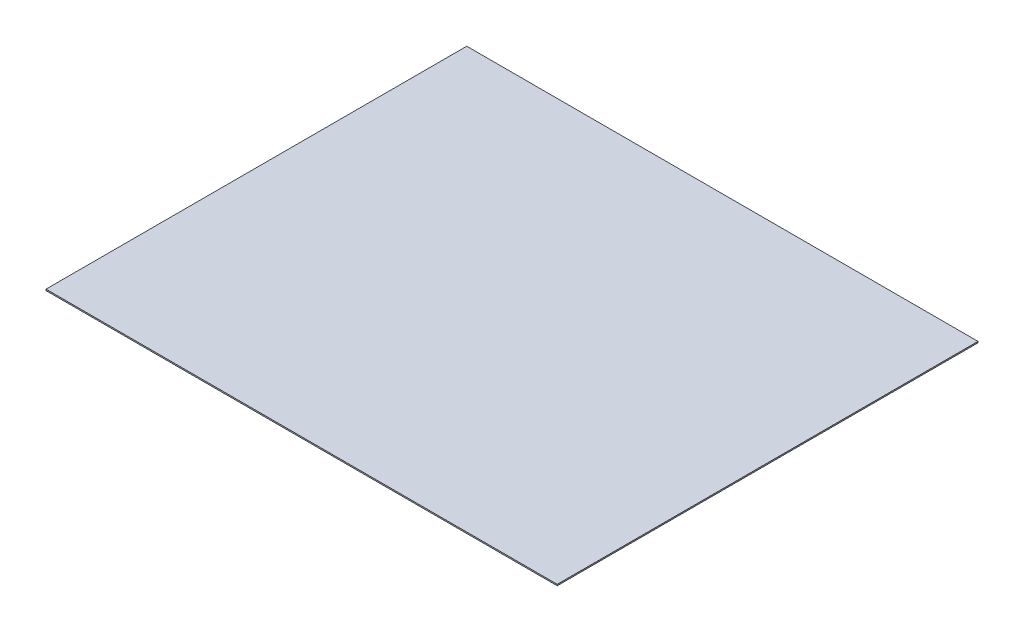
SolidWorks part; units mm, degrees
ref_plane "Front Plane" through (0, 0, 0) normal (0, 0, 1) x (1, 0, 0)
ref_plane "Top Plane" through (0, 0, 0) normal (0, 1, 0) x (1, 0, 0)
ref_plane "Right Plane" through (0, 0, 0) normal (1, 0, 0) x (0, 0, -1)
sketch "Sketch1" plane through (0, 0, 0) normal (0, 1, 0) x (1, 0, 0)
  line L1 (0, 0) -> (625.602, 0)
  line L2 (0, 0) -> (0, 514.8758)
  line L3 (0, 514.8758) -> (625.602, 514.8758)
  line L4 (625.602, 0) -> (625.602, 514.8758)
  dimension "D1" = 514.8758
  dimension "D2" = 625.602
extrude "Boss-Extrude1" add sketch "Sketch1" along normal blind 1.5875
